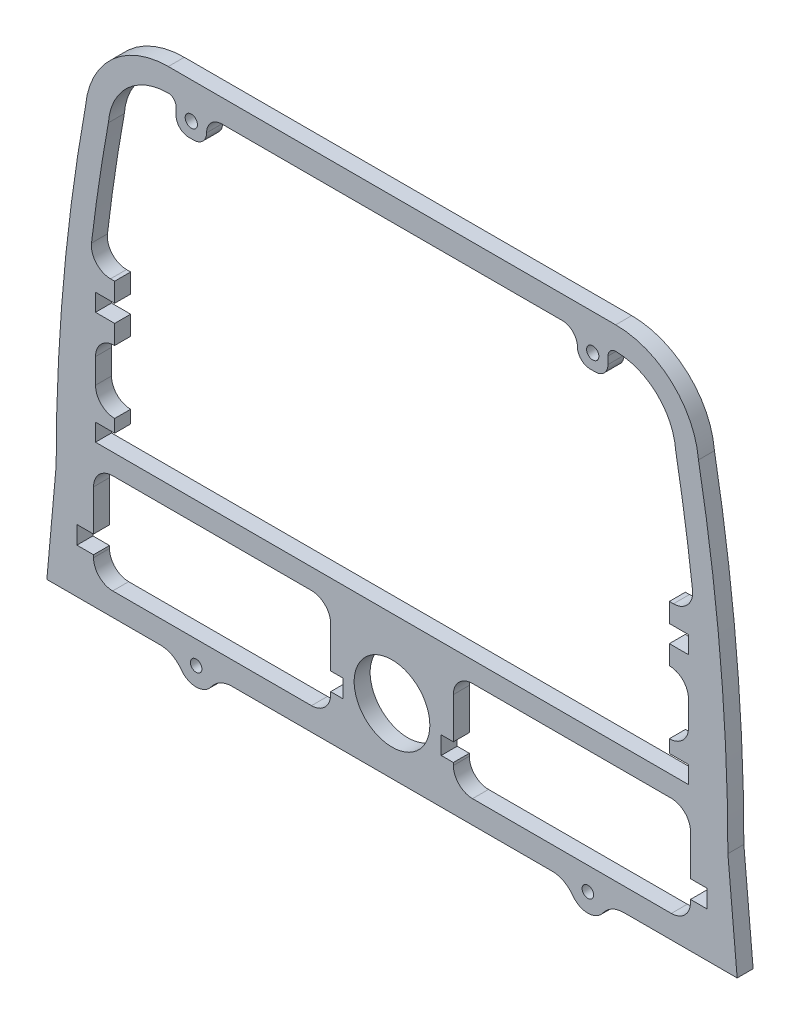
SolidWorks part; units mm, degrees
material "Delrin 2700 NC010, Low Viscosity Acetal Copolymer (SS)"
ref_plane "Front Plane" through (0, 0, 0) normal (0, 0, 1) x (1, 0, 0)
ref_plane "Top Plane" through (0, 0, 0) normal (0, 1, 0) x (1, 0, 0)
ref_plane "Right Plane" through (0, 0, 0) normal (1, 0, 0) x (0, 0, -1)
sketch "Sketch1" plane through (0, 0, 0) normal (0, 0, 1) x (1, 0, 0)
  line L0 (33.3676, -11.9888) -> (34.29, -22.225)
  line L1 (22.225, 27.94) -> (-22.225, 27.94)
  line L2 (-34.29, -22.225) -> (-30.4467, 20.4259) construction
  line L3 (-33.3676, -11.9888) -> (-33.3676, 14.6458) construction
  line L4 (-33.3676, -11.9888) -> (-34.29, -22.225)
  line L5 (16.9079, 25.654) -> (-16.9079, 25.654)
  line L6 (6.096, -17.78) -> (6.096, -19.939)
  line L7 (-29.6529, -19.939) -> (-6.096, -19.939)
  line L8 (-34.29, -22.225) -> (-21.299, -22.225)
  line L9 (-29.6529, -10.033) -> (-29.6529, -16.002)
  line L10 (18.4213, 24.1407) -> (18.4213, 24.1363)
  line L11 (19.6913, 22.8663) -> (20.1867, 22.8663)
  line L12 (21.4567, 24.1363) -> (21.4567, 24.8713)
  line L13 (-21.4567, 24.1363) -> (-21.4567, 24.8713)
  line L14 (-19.6913, 22.8663) -> (-20.1867, 22.8663)
  line L15 (-18.4213, 24.1407) -> (-18.4213, 24.1363)
  line L16 (29.4572, -8.001) -> (-29.4572, -8.001)
  line L17 (29.6529, -10.033) -> (6.096, -10.033)
  line L18 (0, 18.415) -> (0, -18.415) construction
  line L19 (-1007.9925, 0) -> (48992.0075, 0) construction
  line L20 (-6.096, -10.033) -> (-29.6529, -10.033)
  line L21 (19.939, 24.384) -> (21.4567, 24.384) construction
  line L22 (6.096, -19.939) -> (29.6529, -19.939)
  line L23 (-6.096, -10.033) -> (-6.096, -16.002)
  line L24 (5.9491, -2.2098) -> (59.5431, -2.2098) construction
  line L25 (5.9491, -2.2098) -> (5.9491, -11.9888) construction
  line L26 (3.4091, -11.9888) -> (-3.4091, -11.9888) construction
  line L27 (59.5431, -2.2098) -> (59.5431, -11.9888) construction
  line L28 (-31.7887, -19.939) -> (31.7887, -19.939) construction
  line L29 (22.225, 25.654) -> (-22.225, 25.654) construction
  line L30 (-6.096, -19.939) -> (-6.1666, -19.9899)
  line L31 (29.4572, -6.2738) -> (27.5522, -6.2738)
  line L32 (27.5522, -6.2738) -> (27.5522, -5.0038)
  line L33 (-29.6529, -16.002) -> (-31.3039, -16.002)
  line L34 (27.5522, -5.0038) -> (29.4572, -5.0038)
  line L35 (29.4572, 1.27) -> (27.5522, 1.27)
  line L36 (27.5522, 1.27) -> (27.5522, 3.175)
  line L37 (27.5522, 3.175) -> (29.4572, 3.175)
  line L38 (29.4572, 4.9022) -> (27.5522, 4.9022)
  line L39 (19.939, 24.384) -> (18.4213, 24.384) construction
  line L40 (27.5522, 4.9022) -> (27.5522, 6.8072)
  line L41 (27.5522, 6.8072) -> (30.0922, 6.8072)
  line L42 (19.939, 24.384) -> (19.939, 22.8663) construction
  line L43 (6.096, -10.033) -> (6.096, -16.002)
  line L44 (-29.4572, -6.2738) -> (-29.4572, -8.001)
  line L45 (-29.4572, -6.2738) -> (-27.5522, -6.2738)
  line L46 (-27.5522, -6.2738) -> (-27.5522, -5.0038)
  line L47 (-27.5522, -5.0038) -> (-29.4572, -5.0038)
  line L48 (-29.4572, 1.27) -> (-29.4572, -5.0038)
  line L49 (-29.4572, 1.27) -> (-27.5522, 1.27)
  line L50 (-27.5522, 1.27) -> (-27.5522, 3.175)
  line L51 (-27.5522, 3.175) -> (-29.4572, 3.175)
  line L52 (-29.4572, 4.9022) -> (-29.4572, 3.175)
  line L53 (-31.3039, -16.002) -> (-31.3039, -17.78)
  line L54 (-31.3039, -17.78) -> (-29.6529, -17.78)
  line L55 (-6.096, -16.002) -> (-4.8879, -16.002)
  line L56 (-4.8879, -16.002) -> (-4.8879, -17.78)
  line L57 (-4.8879, -17.78) -> (-6.096, -17.78)
  line L58 (-29.6529, -10.033) -> (-29.6529, -19.939) construction
  line L59 (-29.6529, -14.986) -> (-33.4249, -14.986) construction
  line L60 (-29.6529, -14.986) -> (-0.4824, -14.986) construction
  line L61 (-6.096, -17.78) -> (-6.096, -19.939)
  line L62 (-29.6529, -19.939) -> (-29.6529, -17.78)
  line L63 (29.6529, -19.939) -> (29.6529, -17.78)
  line L64 (-31.0816, -12.0913) -> (-31.7887, -19.939) construction
  line L65 (29.6529, -10.033) -> (29.6529, -16.002)
  line L66 (31.3039, -17.78) -> (29.6529, -17.78)
  line L67 (31.3039, -16.002) -> (31.3039, -17.78)
  line L68 (29.6529, -16.002) -> (31.3039, -16.002)
  line L69 (6.096, -16.002) -> (4.8879, -16.002)
  line L70 (4.8879, -16.002) -> (4.8879, -17.78)
  line L71 (4.8879, -17.78) -> (6.096, -17.78)
  line L72 (29.4572, 4.9022) -> (29.4572, 3.175)
  line L73 (31.0816, -12.0913) -> (31.7887, -19.939) construction
  line L74 (29.4572, 1.27) -> (29.4572, -5.0038)
  line L75 (29.4572, -6.2738) -> (29.4572, -8.001)
  line L76 (-29.4572, 4.9022) -> (-27.5522, 4.9022)
  line L77 (-27.5522, 4.9022) -> (-27.5522, 6.8072)
  line L78 (-27.5522, 6.8072) -> (-30.0922, 6.8072)
  line L79 (-17.616, -22.225) -> (17.616, -22.225)
  line L80 (21.299, -22.225) -> (34.29, -22.225)
  line L81 (-34.29, -22.225) -> (34.29, -22.225) construction
  arc A0 (22.225, 27.94) -> (30.4467, 20.4259) centre (22.225, 19.685) cw
  arc A1 (-22.225, 27.94) -> (-30.4467, 20.4259) centre (-22.225, 19.685) ccw
  arc A2 (33.3676, -11.9888) -> (30.4467, 20.4259) centre (-147.9525, -11.9888) ccw
  circle A3 centre (0, -15.748) radius 3.7592
  circle A4 centre (19.4575, -22.225) radius 0.5715
  arc A5 (-33.3676, -11.9888) -> (-30.4467, 20.4259) centre (147.9525, -11.9888) cw
  arc A6 (-17.616, -22.225) -> (-21.299, -22.225) centre (-19.4575, -22.225) cw
  arc A7 (17.616, -22.225) -> (21.299, -22.225) centre (19.4575, -22.225) ccw
  arc A8 (20.1867, 22.8663) -> (21.4567, 24.1363) centre (20.1867, 24.1363) ccw
  circle A9 centre (-19.939, 24.384) radius 0.6096
  circle A10 centre (19.939, 24.384) radius 0.6096
  arc A11 (18.4213, 24.1363) -> (19.6913, 22.8663) centre (19.6913, 24.1363) ccw
  circle A12 centre (-19.4575, -22.225) radius 0.5715
  arc A13 (18.4213, 24.1407) -> (16.9079, 25.654) centre (16.9079, 24.1407) ccw
  arc A14 (22.2416, 25.654) -> (21.4567, 24.8713) centre (22.2394, 24.8713) ccw
  arc A15 (-22.2416, 25.654) -> (-21.4567, 24.8713) centre (-22.2394, 24.8713) cw
  arc A16 (-20.1867, 22.8663) -> (-21.4567, 24.1363) centre (-20.1867, 24.1363) cw
  arc A17 (-18.4213, 24.1363) -> (-19.6913, 22.8663) centre (-19.6913, 24.1363) cw
  arc A18 (-22.2416, 25.654) -> (-28.1777, 20.1262) centre (-22.225, 19.685) ccw
  arc A19 (-18.4213, 24.1407) -> (-16.9079, 25.654) centre (-16.9079, 24.1407) cw
  arc A20 (31.0816, -12.0913) -> (31.0816, -11.9888) centre (-147.9525, -11.9888) ccw
  circle A21 centre (-19.4575, -22.225) radius 1.8415 construction
  arc A23 (22.2416, 25.654) -> (28.1777, 20.1262) centre (22.225, 19.685) cw
  arc A25 (-22.225, 25.654) -> (-28.1777, 20.1262) centre (-22.225, 19.685) ccw construction
  arc A26 (22.225, 25.654) -> (28.1777, 20.1262) centre (22.225, 19.685) cw construction
  arc A28 (-31.0816, -12.0913) -> (-28.1777, 20.1262) centre (147.9525, -11.9888) cw construction
  arc A30 (31.0816, -12.0913) -> (28.1777, 20.1262) centre (-147.9525, -11.9888) ccw construction
  arc A31 (30.0922, 6.8072) -> (28.1777, 20.1262) centre (-147.9525, -11.9888) ccw
  arc A33 (-30.0922, 6.8072) -> (-28.1777, 20.1262) centre (147.9525, -11.9888) cw
  point P0 (0, 0)
  point P1 (0, 27.94)
  point P31 (0, -11.9888)
  point P121 (-30.9018, -14.986)
  point P135 (-17.616, -22.225)
  dimension "D4" = 2.286
  dimension "D6" = 8.255
  dimension "D7" = 19.4575
  dimension "D8" = 50.165
  dimension "D9" = 15.748
  dimension "D5" = 1.2192
  dimension "D17" = 1.143
  dimension "D3" = 7.5184
  dimension "D18" = 1.27
  dimension "D19" = 1.27
  dimension "D26" = 11.176
  dimension "D28" = 0.7827
  dimension "D29" = 1.5133
  dimension "D32" = 1.651
  dimension "D2" = 44.45
  dimension "D10" = 1.27
  dimension "D11" = 1.27
  dimension "D12" = 68.58
  dimension "D13" = 19.939
  dimension "D14" = 22.225
  dimension "D15" = 53.594
  dimension "D16" = 9.779
  dimension "D20" = 6.096
  dimension "D21" = 11.938
  dimension "D22" = 2.032
  dimension "D23" = 1.7272
  dimension "D24" = 1.27
  dimension "D25" = 1.905
  dimension "D27" = 0.4954
  dimension "D30" = 1.905
  dimension "D31" = 1.7272
  dimension "D33" = 1.778
  dimension "D34" = 2.159
  dimension "D35" = 23.5569
  dimension "D36" = 26.416
  dimension "D37" = 1.905
  dimension "D38" = 2.54
extrude "Boss-Extrude1" add sketch "Sketch1" along normal blind 1.5875 contours L8 A12 A4 L0 A2 A0 L1 A1 A5 L4 L74 L16 A18 A15 L13 A16 L14 A17 L15 A19 L5 A13 L10 A11 L11 A8 L12 A14 A23 A20 L22 L43 L17 A10 A9 A3 L20 region at (32.9716, -17.1841, 0)
ref_axis "Axis1" through (0, -15.748, 0) along (0, 0, 1)
fillet "Fillet1" radius 1.905 8 edges at (-6.096, -10.033, 0.7937) (6.096, -10.033, 0.7937) (-6.096, -19.939, 0.7937) (-29.6529, -19.939, 0.7937) (-29.6529, -10.033, 0.7937) (6.096, -19.939, 0.7937) (29.6529, -19.939, 0.7937) (29.6529, -10.033, 0.7937)
fillet "Fillet2" radius 1.905 6 edges at (-29.4572, 1.27, 0.7937) (-29.4572, -5.0038, 0.7937) (-30.0922, 6.8072, 0.7937) (29.4572, -5.0038, 0.7937) (29.4572, 1.27, 0.7937) (30.0922, 6.8072, 0.7937)
fillet "Fillet3" radius 2.54 4 edges at (-17.616, -22.225, 0.7937) (-21.299, -22.225, 0.7937) (17.616, -22.225, 0.7937) (21.299, -22.225, 0.7937)
